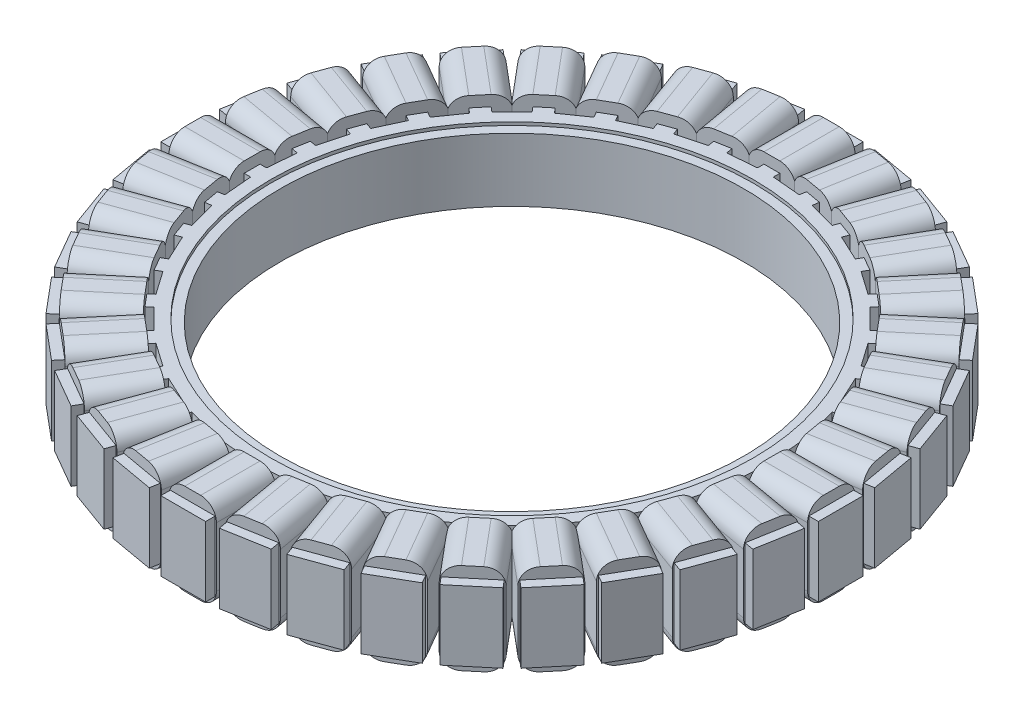
SolidWorks part; units mm, degrees
ref_plane "Front Plane" through (0, 0, 0) normal (0, 0, 1) x (1, 0, 0)
ref_plane "Top Plane" through (0, 0, 0) normal (0, 1, 0) x (1, 0, 0)
ref_plane "Right Plane" through (0, 0, 0) normal (1, 0, 0) x (0, 0, -1)
sketch "Sketch1" plane through (0, 0, 0) normal (0, 1, 0) x (1, 0, 0)
  circle A0 centre (0, 0) radius 29.25
  circle A1 centre (0, 0) radius 30.45
  dimension "D1" = 58.5
  dimension "D2" = 1.2
extrude "Boss-Extrude1" add sketch "Sketch1" along normal mid plane 8
sketch "Sketch2" plane through (0, 0, 0) normal (0, 1, 0) x (1, 0, 0)
  line L0 (0, 0) -> (0, 41.5) construction
  line L1 (-3.6308, 41.5) -> (-10.782, 40.239)
  line L2 (-10.782, 40.239) -> (-17.6057, 37.7554)
  line L3 (-17.6057, 37.7554) -> (-23.8943, 34.1247)
  line L4 (-23.8943, 34.1247) -> (-29.457, 29.457)
  line L5 (-29.457, 29.457) -> (-34.1247, 23.8943)
  line L6 (-34.1247, 23.8943) -> (-37.7554, 17.6057)
  line L7 (-37.7554, 17.6057) -> (-40.239, 10.782)
  line L8 (-40.239, 10.782) -> (-41.5, 3.6308)
  line L9 (-41.5, 3.6308) -> (-41.5, -3.6308)
  line L10 (-41.5, -3.6308) -> (-40.239, -10.782)
  line L11 (-40.239, -10.782) -> (-37.7554, -17.6057)
  line L12 (-37.7554, -17.6057) -> (-34.1247, -23.8943)
  line L13 (-34.1247, -23.8943) -> (-29.457, -29.457)
  line L14 (-29.457, -29.457) -> (-23.8943, -34.1247)
  line L15 (-23.8943, -34.1247) -> (-17.6057, -37.7554)
  line L16 (-17.6057, -37.7554) -> (-10.782, -40.239)
  line L17 (-10.782, -40.239) -> (-3.6308, -41.5)
  line L18 (-3.6308, -41.5) -> (3.6308, -41.5)
  line L19 (3.6308, -41.5) -> (10.782, -40.239)
  line L20 (10.782, -40.239) -> (17.6057, -37.7554)
  line L21 (17.6057, -37.7554) -> (23.8943, -34.1247)
  line L22 (23.8943, -34.1247) -> (29.457, -29.457)
  line L23 (29.457, -29.457) -> (34.1247, -23.8943)
  line L24 (34.1247, -23.8943) -> (37.7554, -17.6057)
  line L25 (37.7554, -17.6057) -> (40.239, -10.782)
  line L26 (40.239, -10.782) -> (41.5, -3.6308)
  line L27 (41.5, -3.6308) -> (41.5, 3.6308)
  line L28 (41.5, 3.6308) -> (40.239, 10.782)
  line L29 (40.239, 10.782) -> (37.7554, 17.6057)
  line L30 (37.7554, 17.6057) -> (34.1247, 23.8943)
  line L31 (34.1247, 23.8943) -> (29.457, 29.457)
  line L32 (29.457, 29.457) -> (23.8943, 34.1247)
  line L33 (23.8943, 34.1247) -> (17.6057, 37.7554)
  line L34 (17.6057, 37.7554) -> (10.782, 40.239)
  line L35 (10.782, 40.239) -> (3.6308, 41.5)
  line L36 (3.6308, 41.5) -> (-3.6308, 41.5)
  circle A1 centre (0, 0) radius 30.45
  circle A2 centre (0, 0) radius 41.5 construction
  circle A3 centre (0, 0) radius 30.45 construction
  dimension "D1" = 83
extrude "Boss-Extrude2" add sketch "Sketch2" along normal mid plane 8.8
sketch "Sketch4" plane through (0, 4.4, 0) normal (0, 1, 0) x (1, 0, 0)
  line L0 (0, 0) -> (0, 41.5) construction
  line L1 (3.6308, 41.5) -> (-3.6308, 41.5) construction
  line L2 (0, 0) -> (3.6308, 41.5) construction
  line L3 (1, 40.3) -> (2.8277, 40.3)
  line L4 (1, 40.3) -> (1, 31.9846)
  line L5 (10.782, 40.239) -> (3.6308, 41.5) construction
  line L6 (1, 31.9846) -> (4.5693, 31.6723)
  line L7 (4.5693, 31.6723) -> (6.0132, 39.8614)
  line L8 (2.8277, 40.3) -> (2.8277, 41.5)
  line L9 (2.8277, 41.5) -> (3.6308, 41.5)
  line L10 (3.6308, 41.5) -> (4.4216, 41.3606)
  line L11 (4.4216, 41.3606) -> (4.2133, 40.1788)
  line L12 (4.2133, 40.1788) -> (6.0132, 39.8614)
  line L13 (7.9828, 39.5141) -> (9.7828, 39.1967)
  line L14 (7.9828, 39.5141) -> (6.5389, 31.325)
  line L15 (6.5389, 31.325) -> (9.9997, 30.3977)
  line L16 (9.9997, 30.3977) -> (12.8437, 38.2116)
  line L17 (9.7828, 39.1967) -> (9.9912, 40.3785)
  line L18 (9.9912, 40.3785) -> (10.782, 40.239)
  line L19 (10.782, 40.239) -> (11.5366, 39.9644)
  line L20 (11.5366, 39.9644) -> (11.1262, 38.8368)
  line L21 (11.1262, 38.8368) -> (12.8437, 38.2116)
  line L22 (14.7231, 37.5276) -> (16.4406, 36.9025)
  line L23 (14.7231, 37.5276) -> (11.8791, 29.7136)
  line L24 (11.8791, 29.7136) -> (15.1263, 28.1994)
  line L25 (15.1263, 28.1994) -> (19.284, 35.4008)
  line L26 (16.4406, 36.9025) -> (16.851, 38.0301)
  line L27 (16.851, 38.0301) -> (17.6057, 37.7554)
  line L28 (17.6057, 37.7554) -> (18.3011, 37.3539)
  line L29 (18.3011, 37.3539) -> (17.7011, 36.3147)
  line L30 (17.7011, 36.3147) -> (19.284, 35.4008)
  line L31 (21.016, 34.4008) -> (22.5989, 33.487)
  line L32 (21.016, 34.4008) -> (16.8583, 27.1994)
  line L33 (16.8583, 27.1994) -> (19.7932, 25.1444)
  line L34 (19.7932, 25.1444) -> (25.1383, 31.5144)
  line L35 (22.5989, 33.487) -> (23.1989, 34.5262)
  line L36 (23.1989, 34.5262) -> (23.8943, 34.1247)
  line L37 (23.8943, 34.1247) -> (24.5095, 33.6085)
  line L38 (24.5095, 33.6085) -> (23.7382, 32.6892)
  line L39 (23.7382, 32.6892) -> (25.1383, 31.5144)
  line L40 (26.6704, 30.2288) -> (28.0705, 29.054)
  line L41 (26.6704, 30.2288) -> (21.3253, 23.8588)
  line L42 (21.3253, 23.8588) -> (23.8588, 21.3253)
  line L43 (23.8588, 21.3253) -> (30.2288, 26.6704)
  line L44 (28.0705, 29.054) -> (28.8418, 29.9732)
  line L45 (28.8418, 29.9732) -> (29.457, 29.457)
  line L46 (29.457, 29.457) -> (29.9732, 28.8418)
  line L47 (29.9732, 28.8418) -> (29.054, 28.0705)
  line L48 (29.054, 28.0705) -> (30.2288, 26.6704)
  line L49 (31.5144, 25.1383) -> (32.6892, 23.7382)
  line L50 (31.5144, 25.1383) -> (25.1444, 19.7932)
  line L51 (25.1444, 19.7932) -> (27.1994, 16.8583)
  line L52 (27.1994, 16.8583) -> (34.4008, 21.016)
  line L53 (32.6892, 23.7382) -> (33.6085, 24.5095)
  line L54 (33.6085, 24.5095) -> (34.1247, 23.8943)
  line L55 (34.1247, 23.8943) -> (34.5262, 23.1989)
  line L56 (34.5262, 23.1989) -> (33.487, 22.5989)
  line L57 (33.487, 22.5989) -> (34.4008, 21.016)
  line L58 (35.4008, 19.284) -> (36.3147, 17.7011)
  line L59 (35.4008, 19.284) -> (28.1994, 15.1263)
  line L60 (28.1994, 15.1263) -> (29.7136, 11.8791)
  line L61 (29.7136, 11.8791) -> (37.5276, 14.7231)
  line L62 (36.3147, 17.7011) -> (37.3539, 18.3011)
  line L63 (37.3539, 18.3011) -> (37.7554, 17.6057)
  line L64 (37.7554, 17.6057) -> (38.0301, 16.851)
  line L65 (38.0301, 16.851) -> (36.9025, 16.4406)
  line L66 (36.9025, 16.4406) -> (37.5276, 14.7231)
  line L67 (38.2116, 12.8437) -> (38.8368, 11.1262)
  line L68 (38.2116, 12.8437) -> (30.3977, 9.9997)
  line L69 (30.3977, 9.9997) -> (31.325, 6.5389)
  line L70 (31.325, 6.5389) -> (39.5141, 7.9828)
  line L71 (38.8368, 11.1262) -> (39.9644, 11.5366)
  line L72 (39.9644, 11.5366) -> (40.239, 10.782)
  line L73 (40.239, 10.782) -> (40.3785, 9.9912)
  line L74 (40.3785, 9.9912) -> (39.1967, 9.7828)
  line L75 (39.1967, 9.7828) -> (39.5141, 7.9828)
  line L76 (39.8614, 6.0132) -> (40.1788, 4.2133)
  line L77 (39.8614, 6.0132) -> (31.6723, 4.5693)
  line L78 (31.6723, 4.5693) -> (31.9846, 1)
  line L79 (31.9846, 1) -> (40.3, 1)
  line L80 (40.1788, 4.2133) -> (41.3606, 4.4216)
  line L81 (41.3606, 4.4216) -> (41.5, 3.6308)
  line L82 (41.5, 3.6308) -> (41.5, 2.8277)
  line L83 (41.5, 2.8277) -> (40.3, 2.8277)
  line L84 (40.3, 2.8277) -> (40.3, 1)
  line L85 (40.3, -1) -> (40.3, -2.8277)
  line L86 (40.3, -1) -> (31.9846, -1)
  line L87 (31.9846, -1) -> (31.6723, -4.5693)
  line L88 (31.6723, -4.5693) -> (39.8614, -6.0132)
  line L89 (40.3, -2.8277) -> (41.5, -2.8277)
  line L90 (41.5, -2.8277) -> (41.5, -3.6308)
  line L91 (41.5, -3.6308) -> (41.3606, -4.4216)
  line L92 (41.3606, -4.4216) -> (40.1788, -4.2133)
  line L93 (40.1788, -4.2133) -> (39.8614, -6.0132)
  line L94 (39.5141, -7.9828) -> (39.1967, -9.7828)
  line L95 (39.5141, -7.9828) -> (31.325, -6.5389)
  line L96 (31.325, -6.5389) -> (30.3977, -9.9997)
  line L97 (30.3977, -9.9997) -> (38.2116, -12.8437)
  line L98 (39.1967, -9.7828) -> (40.3785, -9.9912)
  line L99 (40.3785, -9.9912) -> (40.239, -10.782)
  line L100 (40.239, -10.782) -> (39.9644, -11.5366)
  line L101 (39.9644, -11.5366) -> (38.8368, -11.1262)
  line L102 (38.8368, -11.1262) -> (38.2116, -12.8437)
  line L103 (37.5276, -14.7231) -> (36.9025, -16.4406)
  line L104 (37.5276, -14.7231) -> (29.7136, -11.8791)
  line L105 (29.7136, -11.8791) -> (28.1994, -15.1263)
  line L106 (28.1994, -15.1263) -> (35.4008, -19.284)
  line L107 (36.9025, -16.4406) -> (38.0301, -16.851)
  line L108 (38.0301, -16.851) -> (37.7554, -17.6057)
  line L109 (37.7554, -17.6057) -> (37.3539, -18.3011)
  line L110 (37.3539, -18.3011) -> (36.3147, -17.7011)
  line L111 (36.3147, -17.7011) -> (35.4008, -19.284)
  line L112 (34.4008, -21.016) -> (33.487, -22.5989)
  line L113 (34.4008, -21.016) -> (27.1994, -16.8583)
  line L114 (27.1994, -16.8583) -> (25.1444, -19.7932)
  line L115 (25.1444, -19.7932) -> (31.5144, -25.1383)
  line L116 (33.487, -22.5989) -> (34.5262, -23.1989)
  line L117 (34.5262, -23.1989) -> (34.1247, -23.8943)
  line L118 (34.1247, -23.8943) -> (33.6085, -24.5095)
  line L119 (33.6085, -24.5095) -> (32.6892, -23.7382)
  line L120 (32.6892, -23.7382) -> (31.5144, -25.1383)
  line L121 (30.2288, -26.6704) -> (29.054, -28.0705)
  line L122 (30.2288, -26.6704) -> (23.8588, -21.3253)
  line L123 (23.8588, -21.3253) -> (21.3253, -23.8588)
  line L124 (21.3253, -23.8588) -> (26.6704, -30.2288)
  line L125 (29.054, -28.0705) -> (29.9732, -28.8418)
  line L126 (29.9732, -28.8418) -> (29.457, -29.457)
  line L127 (29.457, -29.457) -> (28.8418, -29.9732)
  line L128 (28.8418, -29.9732) -> (28.0705, -29.054)
  line L129 (28.0705, -29.054) -> (26.6704, -30.2288)
  line L130 (25.1383, -31.5144) -> (23.7382, -32.6892)
  line L131 (25.1383, -31.5144) -> (19.7932, -25.1444)
  line L132 (19.7932, -25.1444) -> (16.8583, -27.1994)
  line L133 (16.8583, -27.1994) -> (21.016, -34.4008)
  line L134 (23.7382, -32.6892) -> (24.5095, -33.6085)
  line L135 (24.5095, -33.6085) -> (23.8943, -34.1247)
  line L136 (23.8943, -34.1247) -> (23.1989, -34.5262)
  line L137 (23.1989, -34.5262) -> (22.5989, -33.487)
  line L138 (22.5989, -33.487) -> (21.016, -34.4008)
  line L139 (19.284, -35.4008) -> (17.7011, -36.3147)
  line L140 (19.284, -35.4008) -> (15.1263, -28.1994)
  line L141 (15.1263, -28.1994) -> (11.8791, -29.7136)
  line L142 (11.8791, -29.7136) -> (14.7231, -37.5276)
  line L143 (17.7011, -36.3147) -> (18.3011, -37.3539)
  line L144 (18.3011, -37.3539) -> (17.6057, -37.7554)
  line L145 (17.6057, -37.7554) -> (16.851, -38.0301)
  line L146 (16.851, -38.0301) -> (16.4406, -36.9025)
  line L147 (16.4406, -36.9025) -> (14.7231, -37.5276)
  line L148 (12.8437, -38.2116) -> (11.1262, -38.8368)
  line L149 (12.8437, -38.2116) -> (9.9997, -30.3977)
  line L150 (9.9997, -30.3977) -> (6.5389, -31.325)
  line L151 (6.5389, -31.325) -> (7.9828, -39.5141)
  line L152 (11.1262, -38.8368) -> (11.5366, -39.9644)
  line L153 (11.5366, -39.9644) -> (10.782, -40.239)
  line L154 (10.782, -40.239) -> (9.9912, -40.3785)
  line L155 (9.9912, -40.3785) -> (9.7828, -39.1967)
  line L156 (9.7828, -39.1967) -> (7.9828, -39.5141)
  line L157 (6.0132, -39.8614) -> (4.2133, -40.1788)
  line L158 (6.0132, -39.8614) -> (4.5693, -31.6723)
  line L159 (4.5693, -31.6723) -> (1, -31.9846)
  line L160 (1, -31.9846) -> (1, -40.3)
  line L161 (4.2133, -40.1788) -> (4.4216, -41.3606)
  line L162 (4.4216, -41.3606) -> (3.6308, -41.5)
  line L163 (3.6308, -41.5) -> (2.8277, -41.5)
  line L164 (2.8277, -41.5) -> (2.8277, -40.3)
  line L165 (2.8277, -40.3) -> (1, -40.3)
  line L166 (-1, -40.3) -> (-2.8277, -40.3)
  line L167 (-1, -40.3) -> (-1, -31.9846)
  line L168 (-1, -31.9846) -> (-4.5693, -31.6723)
  line L169 (-4.5693, -31.6723) -> (-6.0132, -39.8614)
  line L170 (-2.8277, -40.3) -> (-2.8277, -41.5)
  line L171 (-2.8277, -41.5) -> (-3.6308, -41.5)
  line L172 (-3.6308, -41.5) -> (-4.4216, -41.3606)
  line L173 (-4.4216, -41.3606) -> (-4.2133, -40.1788)
  line L174 (-4.2133, -40.1788) -> (-6.0132, -39.8614)
  line L175 (-7.9828, -39.5141) -> (-9.7828, -39.1967)
  line L176 (-7.9828, -39.5141) -> (-6.5389, -31.325)
  line L177 (-6.5389, -31.325) -> (-9.9997, -30.3977)
  line L178 (-9.9997, -30.3977) -> (-12.8437, -38.2116)
  line L179 (-9.7828, -39.1967) -> (-9.9912, -40.3785)
  line L180 (-9.9912, -40.3785) -> (-10.782, -40.239)
  line L181 (-10.782, -40.239) -> (-11.5366, -39.9644)
  line L182 (-11.5366, -39.9644) -> (-11.1262, -38.8368)
  line L183 (-11.1262, -38.8368) -> (-12.8437, -38.2116)
  line L184 (-14.7231, -37.5276) -> (-16.4406, -36.9025)
  line L185 (-14.7231, -37.5276) -> (-11.8791, -29.7136)
  line L186 (-11.8791, -29.7136) -> (-15.1263, -28.1994)
  line L187 (-15.1263, -28.1994) -> (-19.284, -35.4008)
  line L188 (-16.4406, -36.9025) -> (-16.851, -38.0301)
  line L189 (-16.851, -38.0301) -> (-17.6057, -37.7554)
  line L190 (-17.6057, -37.7554) -> (-18.3011, -37.3539)
  line L191 (-18.3011, -37.3539) -> (-17.7011, -36.3147)
  line L192 (-17.7011, -36.3147) -> (-19.284, -35.4008)
  line L193 (-21.016, -34.4008) -> (-22.5989, -33.487)
  line L194 (-21.016, -34.4008) -> (-16.8583, -27.1994)
  line L195 (-16.8583, -27.1994) -> (-19.7932, -25.1444)
  line L196 (-19.7932, -25.1444) -> (-25.1383, -31.5144)
  line L197 (-22.5989, -33.487) -> (-23.1989, -34.5262)
  line L198 (-23.1989, -34.5262) -> (-23.8943, -34.1247)
  line L199 (-23.8943, -34.1247) -> (-24.5095, -33.6085)
  line L200 (-24.5095, -33.6085) -> (-23.7382, -32.6892)
  line L201 (-23.7382, -32.6892) -> (-25.1383, -31.5144)
  line L202 (-26.6704, -30.2288) -> (-28.0705, -29.054)
  line L203 (-26.6704, -30.2288) -> (-21.3253, -23.8588)
  line L204 (-21.3253, -23.8588) -> (-23.8588, -21.3253)
  line L205 (-23.8588, -21.3253) -> (-30.2288, -26.6704)
  line L206 (-28.0705, -29.054) -> (-28.8418, -29.9732)
  line L207 (-28.8418, -29.9732) -> (-29.457, -29.457)
  line L208 (-29.457, -29.457) -> (-29.9732, -28.8418)
  line L209 (-29.9732, -28.8418) -> (-29.054, -28.0705)
  line L210 (-29.054, -28.0705) -> (-30.2288, -26.6704)
  line L211 (-31.5144, -25.1383) -> (-32.6892, -23.7382)
  line L212 (-31.5144, -25.1383) -> (-25.1444, -19.7932)
  line L213 (-25.1444, -19.7932) -> (-27.1994, -16.8583)
  line L214 (-27.1994, -16.8583) -> (-34.4008, -21.016)
  line L215 (-32.6892, -23.7382) -> (-33.6085, -24.5095)
  line L216 (-33.6085, -24.5095) -> (-34.1247, -23.8943)
  line L217 (-34.1247, -23.8943) -> (-34.5262, -23.1989)
  line L218 (-34.5262, -23.1989) -> (-33.487, -22.5989)
  line L219 (-33.487, -22.5989) -> (-34.4008, -21.016)
  line L220 (-35.4008, -19.284) -> (-36.3147, -17.7011)
  line L221 (-35.4008, -19.284) -> (-28.1994, -15.1263)
  line L222 (-28.1994, -15.1263) -> (-29.7136, -11.8791)
  line L223 (-29.7136, -11.8791) -> (-37.5276, -14.7231)
  line L224 (-36.3147, -17.7011) -> (-37.3539, -18.3011)
  line L225 (-37.3539, -18.3011) -> (-37.7554, -17.6057)
  line L226 (-37.7554, -17.6057) -> (-38.0301, -16.851)
  line L227 (-38.0301, -16.851) -> (-36.9025, -16.4406)
  line L228 (-36.9025, -16.4406) -> (-37.5276, -14.7231)
  line L229 (-38.2116, -12.8437) -> (-38.8368, -11.1262)
  line L230 (-38.2116, -12.8437) -> (-30.3977, -9.9997)
  line L231 (-30.3977, -9.9997) -> (-31.325, -6.5389)
  line L232 (-31.325, -6.5389) -> (-39.5141, -7.9828)
  line L233 (-38.8368, -11.1262) -> (-39.9644, -11.5366)
  line L234 (-39.9644, -11.5366) -> (-40.239, -10.782)
  line L235 (-40.239, -10.782) -> (-40.3785, -9.9912)
  line L236 (-40.3785, -9.9912) -> (-39.1967, -9.7828)
  line L237 (-39.1967, -9.7828) -> (-39.5141, -7.9828)
  line L238 (-39.8614, -6.0132) -> (-40.1788, -4.2133)
  line L239 (-39.8614, -6.0132) -> (-31.6723, -4.5693)
  line L240 (-31.6723, -4.5693) -> (-31.9846, -1)
  line L241 (-31.9846, -1) -> (-40.3, -1)
  line L242 (-40.1788, -4.2133) -> (-41.3606, -4.4216)
  line L243 (-41.3606, -4.4216) -> (-41.5, -3.6308)
  line L244 (-41.5, -3.6308) -> (-41.5, -2.8277)
  line L245 (-41.5, -2.8277) -> (-40.3, -2.8277)
  line L246 (-40.3, -2.8277) -> (-40.3, -1)
  line L247 (-40.3, 1) -> (-40.3, 2.8277)
  line L248 (-40.3, 1) -> (-31.9846, 1)
  line L249 (-31.9846, 1) -> (-31.6723, 4.5693)
  line L250 (-31.6723, 4.5693) -> (-39.8614, 6.0132)
  line L251 (-40.3, 2.8277) -> (-41.5, 2.8277)
  line L252 (-41.5, 2.8277) -> (-41.5, 3.6308)
  line L253 (-41.5, 3.6308) -> (-41.3606, 4.4216)
  line L254 (-41.3606, 4.4216) -> (-40.1788, 4.2133)
  line L255 (-40.1788, 4.2133) -> (-39.8614, 6.0132)
  line L256 (-39.5141, 7.9828) -> (-39.1967, 9.7828)
  line L257 (-39.5141, 7.9828) -> (-31.325, 6.5389)
  line L258 (-31.325, 6.5389) -> (-30.3977, 9.9997)
  line L259 (-30.3977, 9.9997) -> (-38.2116, 12.8437)
  line L260 (-39.1967, 9.7828) -> (-40.3785, 9.9912)
  line L261 (-40.3785, 9.9912) -> (-40.239, 10.782)
  line L262 (-40.239, 10.782) -> (-39.9644, 11.5366)
  line L263 (-39.9644, 11.5366) -> (-38.8368, 11.1262)
  line L264 (-38.8368, 11.1262) -> (-38.2116, 12.8437)
  line L265 (-37.5276, 14.7231) -> (-36.9025, 16.4406)
  line L266 (-37.5276, 14.7231) -> (-29.7136, 11.8791)
  line L267 (-29.7136, 11.8791) -> (-28.1994, 15.1263)
  line L268 (-28.1994, 15.1263) -> (-35.4008, 19.284)
  line L269 (-36.9025, 16.4406) -> (-38.0301, 16.851)
  line L270 (-38.0301, 16.851) -> (-37.7554, 17.6057)
  line L271 (-37.7554, 17.6057) -> (-37.3539, 18.3011)
  line L272 (-37.3539, 18.3011) -> (-36.3147, 17.7011)
  line L273 (-36.3147, 17.7011) -> (-35.4008, 19.284)
  line L274 (-34.4008, 21.016) -> (-33.487, 22.5989)
  line L275 (-34.4008, 21.016) -> (-27.1994, 16.8583)
  line L276 (-27.1994, 16.8583) -> (-25.1444, 19.7932)
  line L277 (-25.1444, 19.7932) -> (-31.5144, 25.1383)
  line L278 (-33.487, 22.5989) -> (-34.5262, 23.1989)
  line L279 (-34.5262, 23.1989) -> (-34.1247, 23.8943)
  line L280 (-34.1247, 23.8943) -> (-33.6085, 24.5095)
  line L281 (-33.6085, 24.5095) -> (-32.6892, 23.7382)
  line L282 (-32.6892, 23.7382) -> (-31.5144, 25.1383)
  line L283 (-30.2288, 26.6704) -> (-29.054, 28.0705)
  line L284 (-30.2288, 26.6704) -> (-23.8588, 21.3253)
  line L285 (-23.8588, 21.3253) -> (-21.3253, 23.8588)
  line L286 (-21.3253, 23.8588) -> (-26.6704, 30.2288)
  line L287 (-29.054, 28.0705) -> (-29.9732, 28.8418)
  line L288 (-29.9732, 28.8418) -> (-29.457, 29.457)
  line L289 (-29.457, 29.457) -> (-28.8418, 29.9732)
  line L290 (-28.8418, 29.9732) -> (-28.0705, 29.054)
  line L291 (-28.0705, 29.054) -> (-26.6704, 30.2288)
  line L292 (-25.1383, 31.5144) -> (-23.7382, 32.6892)
  line L293 (-25.1383, 31.5144) -> (-19.7932, 25.1444)
  line L294 (-19.7932, 25.1444) -> (-16.8583, 27.1994)
  line L295 (-16.8583, 27.1994) -> (-21.016, 34.4008)
  line L296 (-23.7382, 32.6892) -> (-24.5095, 33.6085)
  line L297 (-24.5095, 33.6085) -> (-23.8943, 34.1247)
  line L298 (-23.8943, 34.1247) -> (-23.1989, 34.5262)
  line L299 (-23.1989, 34.5262) -> (-22.5989, 33.487)
  line L300 (-22.5989, 33.487) -> (-21.016, 34.4008)
  line L301 (-19.284, 35.4008) -> (-17.7011, 36.3147)
  line L302 (-19.284, 35.4008) -> (-15.1263, 28.1994)
  line L303 (-15.1263, 28.1994) -> (-11.8791, 29.7136)
  line L304 (-11.8791, 29.7136) -> (-14.7231, 37.5276)
  line L305 (-17.7011, 36.3147) -> (-18.3011, 37.3539)
  line L306 (-18.3011, 37.3539) -> (-17.6057, 37.7554)
  line L307 (-17.6057, 37.7554) -> (-16.851, 38.0301)
  line L308 (-16.851, 38.0301) -> (-16.4406, 36.9025)
  line L309 (-16.4406, 36.9025) -> (-14.7231, 37.5276)
  line L310 (-12.8437, 38.2116) -> (-11.1262, 38.8368)
  line L311 (-12.8437, 38.2116) -> (-9.9997, 30.3977)
  line L312 (-9.9997, 30.3977) -> (-6.5389, 31.325)
  line L313 (-6.5389, 31.325) -> (-7.9828, 39.5141)
  line L314 (-11.1262, 38.8368) -> (-11.5366, 39.9644)
  line L315 (-11.5366, 39.9644) -> (-10.782, 40.239)
  line L316 (-10.782, 40.239) -> (-9.9912, 40.3785)
  line L317 (-9.9912, 40.3785) -> (-9.7828, 39.1967)
  line L318 (-9.7828, 39.1967) -> (-7.9828, 39.5141)
  line L319 (-6.0132, 39.8614) -> (-4.2133, 40.1788)
  line L320 (-6.0132, 39.8614) -> (-4.5693, 31.6723)
  line L321 (-4.5693, 31.6723) -> (-1, 31.9846)
  line L322 (-1, 31.9846) -> (-1, 40.3)
  line L323 (-4.2133, 40.1788) -> (-4.4216, 41.3606)
  line L324 (-4.4216, 41.3606) -> (-3.6308, 41.5)
  line L325 (-3.6308, 41.5) -> (-2.8277, 41.5)
  line L326 (-2.8277, 41.5) -> (-2.8277, 40.3)
  line L327 (-2.8277, 40.3) -> (-1, 40.3)
  circle A0 centre (0, 0) radius 30.45 construction
  point P337 (0, 0)
  dimension "D1" = 31.95
  dimension "D2" = 1.2
  dimension "D3" = 1
  dimension "D4" = 1.6
  dimension "D5" = 36
extrude "Cut-Extrude1" cut sketch "Sketch4" against normal up to surface (8.8 mm away) up to face at (0, -4.4, 0)
sketch "Sketch5" plane through (0, 0, -40.3) normal (0, 0, 1) x (1, 0, 0)
  line L0 (1, 5.75) -> (-1, 5.75)
  line L1 (-3, -5.75) -> (3, -5.75) construction
  line L2 (-3, -5.75) -> (-3, 5.75) construction
  line L3 (-3, 5.75) -> (3, 5.75) construction
  line L4 (3, -5.75) -> (3, 5.75) construction
  line L5 (-3, -5.75) -> (3, 5.75) construction
  line L6 (-3, 5.75) -> (3, -5.75) construction
  line L7 (-3, 3.75) -> (-3, -3.75)
  line L8 (3, 3.75) -> (3, -3.75)
  line L9 (1, -5.75) -> (-1, -5.75)
  arc A0 (-1, -5.75) -> (-3, -3.75) centre (-1, -3.75) cw
  arc A1 (1, -5.75) -> (3, -3.75) centre (1, -3.75) ccw
  arc A2 (3, 3.75) -> (1, 5.75) centre (1, 3.75) ccw
  arc A3 (-1, 5.75) -> (-3, 3.75) centre (-1, 3.75) ccw
  point P0 (0, 0)
  dimension "D3" = 2
  dimension "D1" = 11.5
  dimension "D2" = 6
extrude "Boss-Extrude3" add sketch "Sketch5" along normal blind 7.5
pattern_circular "CirPattern1" count 36 over 360 of "Boss-Extrude3"
